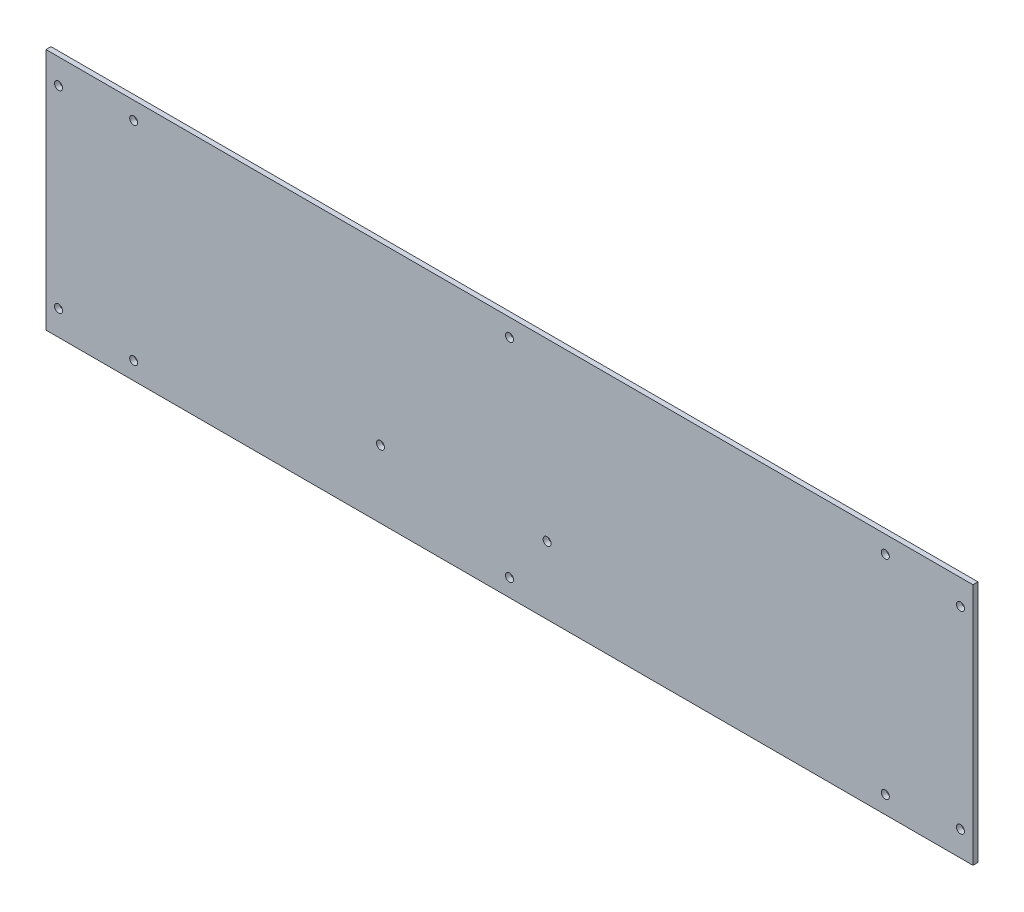
SolidWorks part; units mm, degrees
ref_plane "Front Plane" through (0, 0, 0) normal (1, 0, 0) x (0, 1, 0)
ref_plane "Top Plane" through (0, 0, 0) normal (0, 0, 1) x (0, 1, 0)
ref_plane "Right Plane" through (0, 0, 0) normal (0, 1, 0) x (-1, 0, 0)
sketch "Sketch1" plane through (0, 0, 0) normal (0, 0, 1) x (0, 1, 0)
  line L0 (0, 185) -> (97, 185) construction
  line L1 (0, 0) -> (97, 0)
  line L2 (0, 0) -> (0, 370)
  line L3 (0, 370) -> (97, 370)
  line L4 (97, 0) -> (97, 370)
  circle A0 centre (10, 5) radius 1.6
  circle A1 centre (87, 5) radius 1.6
  circle A2 centre (10, 365) radius 1.6
  circle A3 centre (87, 365) radius 1.6
  circle A4 centre (90, 185) radius 1.6
  circle A5 centre (90, 35) radius 1.6
  circle A6 centre (90, 335) radius 1.6
  circle A7 centre (27, 236.5) radius 1.6
  circle A8 centre (27, 170) radius 1.6
  circle A9 centre (7, 185) radius 1.6
  circle A10 centre (7, 335) radius 1.6
  circle A11 centre (7, 35) radius 1.6
  point P31 (0, 0)
  point P32 (0, 0)
  dimension "D3" = 3.2
  dimension "D8" = 150
  dimension "D11" = 27
  dimension "D14" = 7
  dimension "D1" = 97
  dimension "D2" = 370
  dimension "D4" = 5
  dimension "D5" = 5
  dimension "D6" = 10
  dimension "D7" = 10
  dimension "D9" = 150
  dimension "D10" = 7
  dimension "D12" = 66.5
  dimension "D13" = 170
base flange "Base-Flange1" sketch "Sketch1" thickness 2 reverse thickness direction no parameters "D1"=0.9652
sketch "Bend-Lines1" [suppressed] plane through (0, 0, 0) normal (0, 1, 0) x (-1, 0, 0)
sketch "Bounding-Box1" [suppressed] plane through (0, 0, 0) normal (0, 1, 0) x (-1, 0, 0)
sheet metal parameters "Sheet-Metal1" thickness 2 parameters "D1"=0.9652
flat pattern "Flat-Pattern1" [suppressed]
sketch "Bend-Lines2" plane through (0, 0, 0) normal (0, 1, 0) x (-1, 0, 0)
sketch3d "Bounding-Box2" [suppressed]
  line L0 (0, -370, 0) -> (0, 0, 0) construction
  line L1 (-97, -370, 0) -> (-97, 0, 0) construction
  line L2 (0, -370, 0) -> (-97, -370, 0) construction
  line L3 (0, 0, 0) -> (-97, 0, 0) construction
